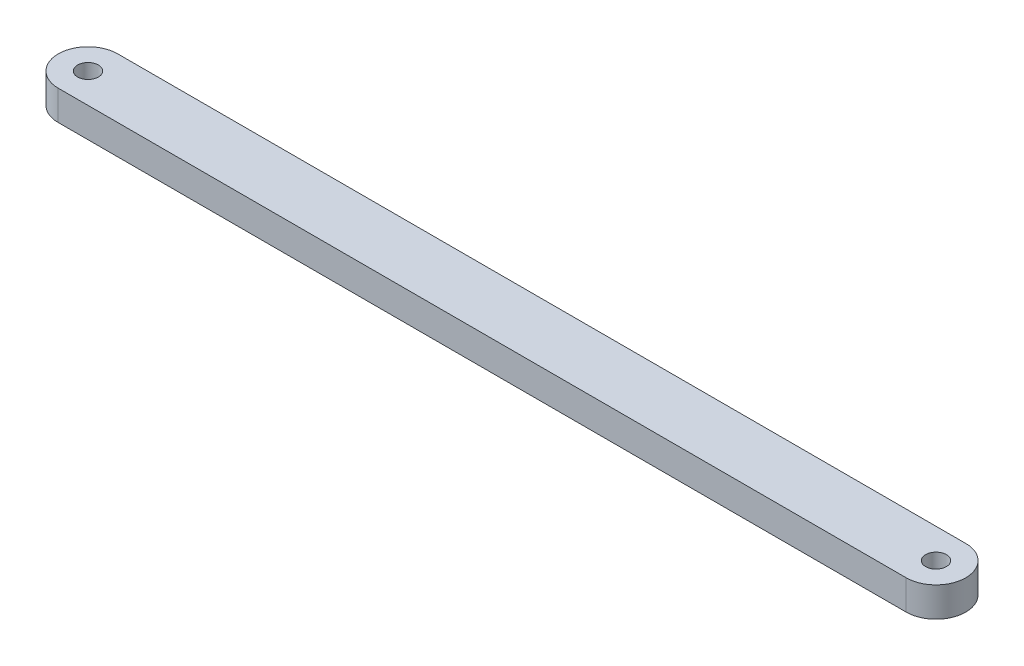
SolidWorks part; units mm, degrees
ref_plane "Front Plane" through (0, 0, 0) normal (0, 0, 1) x (1, 0, 0)
ref_plane "Top Plane" through (0, 0, 0) normal (0, 1, 0) x (1, 0, 0)
ref_plane "Right Plane" through (0, 0, 0) normal (1, 0, 0) x (0, 0, -1)
sketch "Sketch1" plane through (0, 0, 0) normal (0, 1, 0) x (1, 0, 0)
  line L0 (-142.5, 0) -> (142.5, 0) construction
  line L1 (-142.5, 10) -> (142.5, 10)
  line L2 (-142.5, -10) -> (142.5, -10)
  arc A0 (-142.5, 10) -> (-142.5, -10) centre (-142.5, 0) ccw
  arc A1 (142.5, -10) -> (142.5, 10) centre (142.5, 0) ccw
  circle A2 centre (-142.5, 0) radius 3.5
  circle A3 centre (142.5, 0) radius 3.5
  point P2 (0, 0)
  dimension "D3" = 7
  dimension "D4" = 7
  dimension "D1" = 285
  dimension "D2" = 20
extrude "Boss-Extrude1" add sketch "Sketch1" along normal blind 10
equation "\"D4@Sketch1\"=\"D3@Sketch1\""
